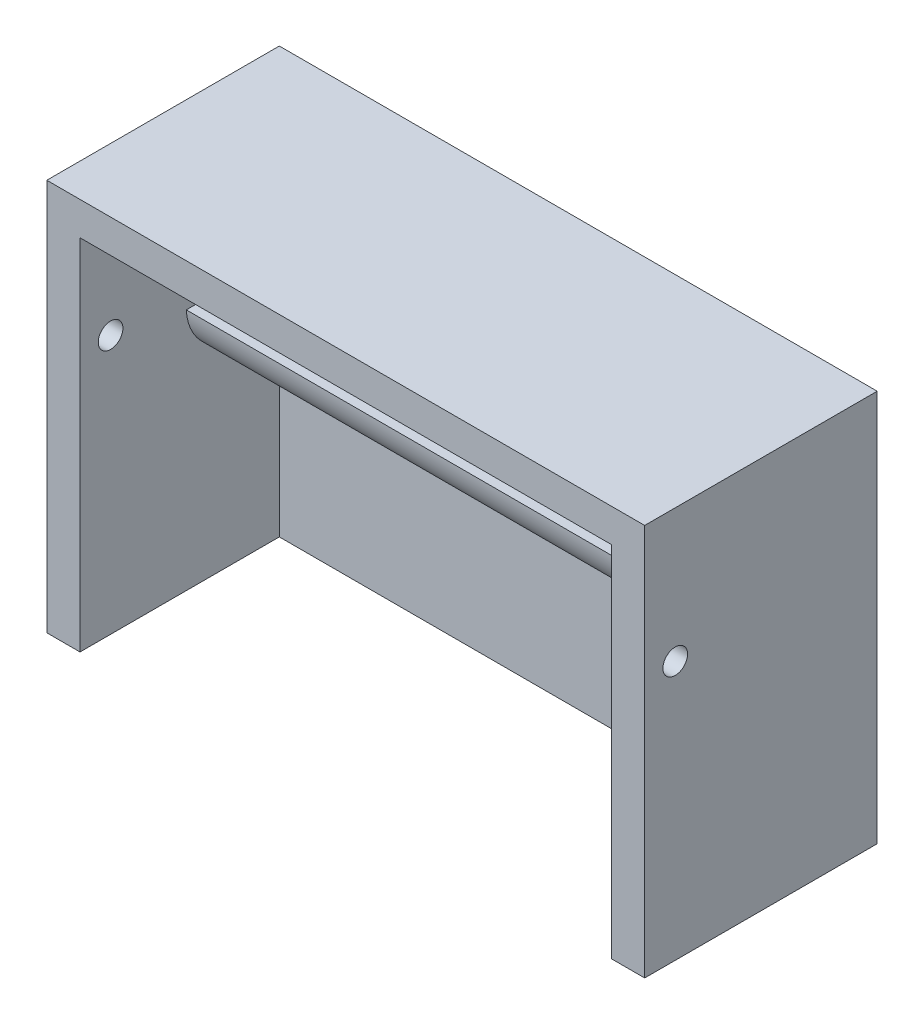
SolidWorks part; units mm, degrees
ref_plane "Front Plane" through (0, 0, 0) normal (0, 0, 1) x (1, 0, 0)
ref_plane "Top Plane" through (0, 0, 0) normal (0, 1, 0) x (1, 0, 0)
ref_plane "Right Plane" through (0, 0, 0) normal (1, 0, 0) x (0, 0, -1)
sketch "Sketch1" plane through (0, 0, 0) normal (0, 0, 1) x (1, 0, 0)
  line L0 (0, 43.931) -> (50.8, 43.931)
  line L1 (50.8, 43.931) -> (50.8, -24.649)
  line L2 (50.8, -24.649) -> (57.15, -24.649)
  line L3 (57.15, -24.649) -> (57.15, 50.281)
  line L4 (57.15, 50.281) -> (0, 50.281)
  line L5 (0, 50.281) -> (0, 43.931)
  dimension "D1" = 6.35
  dimension "D2" = 6.35
  dimension "D3" = 68.58
  dimension "D4" = 50.8
extrude "Boss-Extrude1" add sketch "Sketch1" along normal blind 44.45 contours L4 L5 L0 L1 L2 L3
sketch "Sketch2" plane through (0, 43.931, 0) normal (0, -1, 0) x (1, 0, 0)
  line L0 (50.8, 44.45) -> (50.8, 0) construction
  line L1 (0, 0) -> (50.8, 0)
  line L2 (0, 0) -> (0, 6.35)
  line L3 (0, 6.35) -> (50.8, 6.35)
  line L4 (50.8, 0) -> (50.8, 6.35)
  dimension "D1" = 6.35
extrude "Boss-Extrude2" add sketch "Sketch2" along normal blind 68.58
sketch "Sketch3" plane through (57.15, 0, 0) normal (1, 0, 0) x (0, 0, -1)
  line L0 (-44.45, -24.649) -> (0, -24.649) construction
  line L1 (-44.45, -24.649) -> (-44.45, 50.281) construction
  circle A0 centre (-38.608, 24.881) radius 2.3559
  dimension "D1" = 4.7117
  dimension "D2" = 49.53
  dimension "D3" = 5.842
extrude "Cut-Extrude1" cut sketch "Sketch3" against normal up to next
mirror "Mirror1" about plane through (0, 0, 0) normal (1, 0, 0) of "Cut-Extrude1", "Boss-Extrude2", "Boss-Extrude1"
sketch "Sketch4" plane through (0, 0, 6.35) normal (0, 0, 1) x (1, 0, 0)
  line L0 (-50.8, 43.931) -> (-50.8, -24.649) construction
  line L1 (-50.8, 21.833) -> (50.8, 21.833)
  line L2 (-50.8, 21.833) -> (-50.8, 12.181)
  line L3 (-50.8, 12.181) -> (50.8, 12.181)
  line L4 (50.8, 21.833) -> (50.8, 12.181)
  line L5 (50.8, 43.931) -> (50.8, -24.649) construction
  line L6 (50.8, -24.649) -> (-50.8, -24.649) construction
  dimension "D1" = 46.482
  dimension "D2" = 36.83
extrude "Boss-Extrude3" add sketch "Sketch4" along normal blind 17.78
fillet "Fillet1" radius 10.16 1 edges at (0, 12.181, 24.13)
